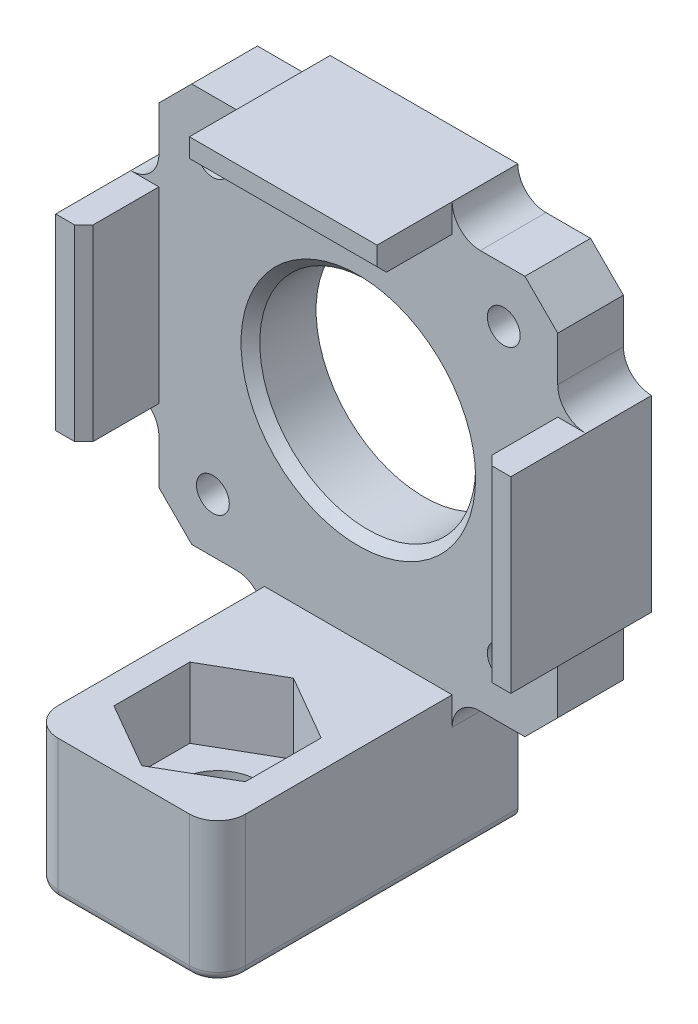
SolidWorks part; units mm, degrees
ref_plane "Plan de face" through (0, 0, 0) normal (0, 0, 1) x (1, 0, 0)
ref_plane "Plan de dessus" through (0, 0, 0) normal (0, 1, 0) x (1, 0, 0)
ref_plane "Plan de droite" through (0, 0, 0) normal (1, 0, 0) x (0, 0, -1)
sketch "Esquisse1" plane through (0, 0, 0) normal (0, 0, 1) x (1, 0, 0)
  line L0 (-17.75, 21.25) -> (-21.25, 17.75)
  line L1 (17.75, 21.25) -> (-17.75, 21.25)
  line L2 (21.25, 17.75) -> (21.25, -17.75)
  line L4 (-21.25, 17.75) -> (-21.25, -17.75)
  line L5 (21.25, 21.25) -> (-21.25, -21.25) construction
  line L6 (21.25, -21.25) -> (-21.25, 21.25) construction
  line L7 (21.25, 17.75) -> (17.75, 21.25)
  line L8 (-17.75, -21.25) -> (-21.25, -17.75)
  line L9 (21.25, -17.75) -> (17.75, -21.25)
  line L10 (-17.75, -21.25) -> (17.75, -21.25)
  line L13 (15.5, 15.5) -> (-15.5, 15.5) construction
  line L14 (15.5, 15.5) -> (15.5, -15.5) construction
  line L15 (15.5, -15.5) -> (-15.5, -15.5) construction
  line L16 (-15.5, 15.5) -> (-15.5, -15.5) construction
  line L17 (15.5, 15.5) -> (-15.5, -15.5) construction
  line L18 (15.5, -15.5) -> (-15.5, 15.5) construction
  line L19 (0, 37.3199) -> (0, -37.3199) construction
  line L20 (-53.6764, 0) -> (53.6764, 0) construction
  circle A0 centre (0, 0) radius 11.5
  circle A1 centre (-15.5, 15.5) radius 1.75
  circle A2 centre (15.5, 15.5) radius 1.75
  circle A3 centre (15.5, -15.5) radius 1.75
  circle A4 centre (-15.5, -15.5) radius 1.75
  point P0 (0, 0)
  point P24 (-21.25, 0)
  dimension "D3" = 23
  dimension "D4" = 3.5
  dimension "D2" = 42.5
  dimension "D5" = 42.5
  dimension "D10" = 21.25
  dimension "D18" = 31
  dimension "D19" = 31
extrude "Boss.-Extru.1" add sketch "Esquisse1" along normal blind 7
sketch "Esquisse2" plane through (0, 0, 0) normal (0, 0, -1) x (-1, 0, 0)
  line L0 (-17.75, 21.25) -> (17.75, 21.25) construction
  line L1 (-10, 21.25) -> (10, 21.25)
  line L2 (-10, 21.25) -> (-10, 24.25)
  line L3 (-10, 24.25) -> (10, 24.25)
  line L4 (10, 21.25) -> (10, 24.25)
  line L5 (24.25, 10) -> (24.25, -10)
  line L6 (21.25, -10) -> (24.25, -10)
  line L7 (21.25, 10) -> (24.25, 10)
  line L8 (21.25, 10) -> (21.25, -10)
  line L13 (-24.25, -10) -> (-24.25, 10)
  line L14 (-21.25, 10) -> (-24.25, 10)
  line L15 (-21.25, -10) -> (-24.25, -10)
  line L16 (-21.25, -10) -> (-21.25, 10)
  line L17 (10, -21.25) -> (-10, -21.25) [skipped]
  line L18 (10, -24.25) -> (-10, -24.25) [skipped]
  line L19 (10, -21.25) -> (10, -24.25) [skipped]
  line L20 (-10, -21.25) -> (-10, -24.25) [skipped]
  line L21 (-21.25, -17.75) -> (-21.25, 17.75) construction
  line L22 (21.25, 17.75) -> (21.25, -17.75) construction
  point P6 (0, 24.25)
  point P23 (0, 0)
  dimension "D1" = 20
  dimension "D2" = 3
  dimension "D3" = 4
extrude "Boss.-Extru.2" add sketch "Esquisse2" against normal blind 15
sketch "Esquisse3" plane through (0, 0, 0) normal (0, 0, -1) x (-1, 0, 0)
  line L1 (-10, -21.25) -> (10, -21.25)
  line L2 (-10, -21.25) -> (-10, -36.25)
  line L3 (-10, -36.25) -> (10, -36.25)
  line L4 (10, -21.25) -> (10, -36.25)
  line L5 (17.75, -21.25) -> (-17.75, -21.25) construction
  point P6 (0, -36.25)
  dimension "D1" = 20
  dimension "D2" = 15
extrude "Boss.-Extru.3" add sketch "Esquisse3" against normal blind 32
fillet "Congé1" radius 3 8 edges at (-21.25, -10, 3.5) (-21.25, 10, 3.5) (-10, 21.25, 3.5) (10, 21.25, 3.5) (21.25, 10, 3.5) (21.25, -10, 3.5) (10, -21.25, 3.5) (-10, -21.25, 3.5)
fillet "Congé2" radius 3 2 edges at (10, -28.75, 32) (-10, -28.75, 32)
chamfer "Chanfrein1" distance 1 angle 45 4 edges at (11.5, 0, 7) (21.25, 0, 15) (0, 21.25, 15) (-21.25, 0, 15)
sketch "Esquisse4" plane through (0, -36.25, 0) normal (0, -1, 0) x (-1, 0, 0)
  line L0 (-7, -32) -> (7, -32) construction
  circle A0 centre (0, -22) radius 4.25
  point P4 (0, -32)
  dimension "D2" = 8.5
  dimension "D1" = 10
extrude "Enlèv. mat.-Extru.1" cut sketch "Esquisse4" against normal up to surface (15 mm away) up to face at (0, -21.25, 22.8738)
fillet "Congé3" radius 1 5 edges at (10, -36.25, 14.5) (9.1213, -36.25, 31.1213) (0, -36.25, 32) (-9.1213, -36.25, 31.1213) (-10, -36.25, 14.5)
sketch "Esquisse5" plane through (0, -21.25, 0) normal (0, 1, 0) x (1, 0, 0)
  line L1 (0, -30.0829) -> (7, -26.0415)
  line L2 (7, -26.0415) -> (7, -17.9585)
  line L3 (7, -17.9585) -> (0, -13.9171)
  line L4 (0, -13.9171) -> (-7, -17.9585)
  line L5 (-7, -17.9585) -> (-7, -26.0415)
  line L6 (-7, -26.0415) -> (0, -30.0829)
  circle A0 centre (0, -22) radius 7 construction
  dimension "D1" = 14
extrude "Enlèv. mat.-Extru.2" cut sketch "Esquisse5" against normal blind 7.5
